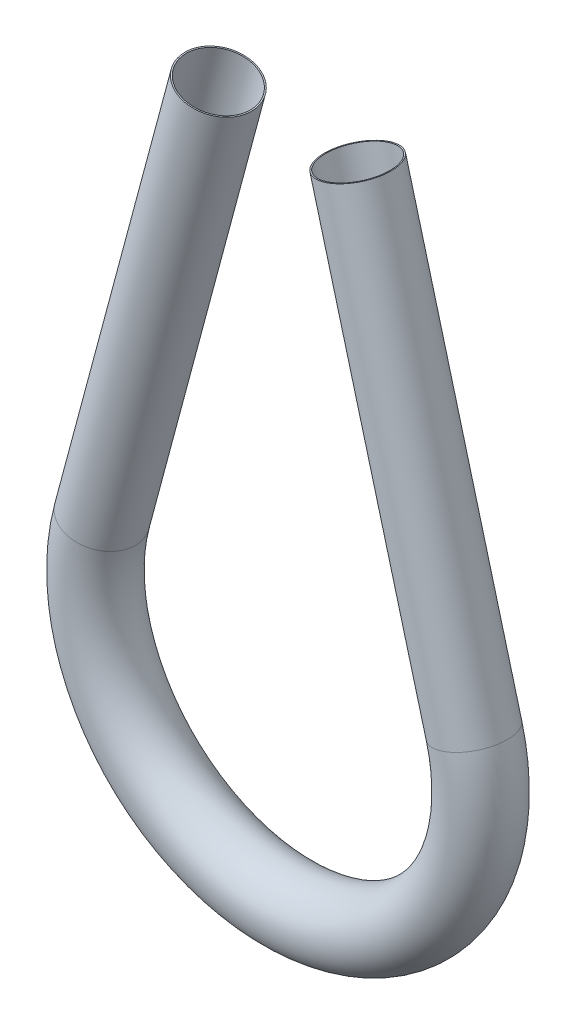
SolidWorks part; units mm, degrees
material "PET"
ref_plane "Front Plane" through (0, 0, 0) normal (0, 0, 1) x (1, 0, 0)
ref_plane "Top Plane" through (0, 0, 0) normal (0, 1, 0) x (1, 0, 0)
ref_plane "Right Plane" through (0, 0, 0) normal (1, 0, 0) x (0, 0, -1)
sketch "Sketch1" plane through (0, 0, 0) normal (0, 0, 1) x (1, 0, 0)
  line L0 (-138.9852, -15.4299) -> (-159.619, -92.4363) construction
  line L1 (-109.0238, -15.4299) -> (-88.39, -92.4363) construction
  line L2 (-137.3417, -9.2963) -> (-159.619, -92.4363)
  line L3 (-110.6673, -9.2963) -> (-88.39, -92.4363)
  arc A0 (-159.619, -92.4363) -> (-88.39, -92.4363) centre (-124.0045, -101.9792) ccw construction
  arc A1 (-159.619, -92.4363) -> (-88.39, -92.4363) centre (-124.0045, -101.9792) ccw
  dimension "D1" = 6.35
  dimension "D2" = 6.35
ref_plane "Plane1" through (-110.6673, -9.2963, 0) normal (0.2588, -0.9659, 0) x (-0.9659, -0.2588, 0)
sketch "Sketch2" plane through (-110.6673, -9.2963, 0) normal (0.2588, -0.9659, 0) x (-0.9659, -0.2588, 0)
  circle A0 centre (0, 0) radius 6.35
  circle A1 centre (0, 0) radius 6.604
  dimension "D1" = 12.7
  dimension "D2" = 0.254
sweep "Sweep1" add profiles "Sketch2" path "Sketch1"
